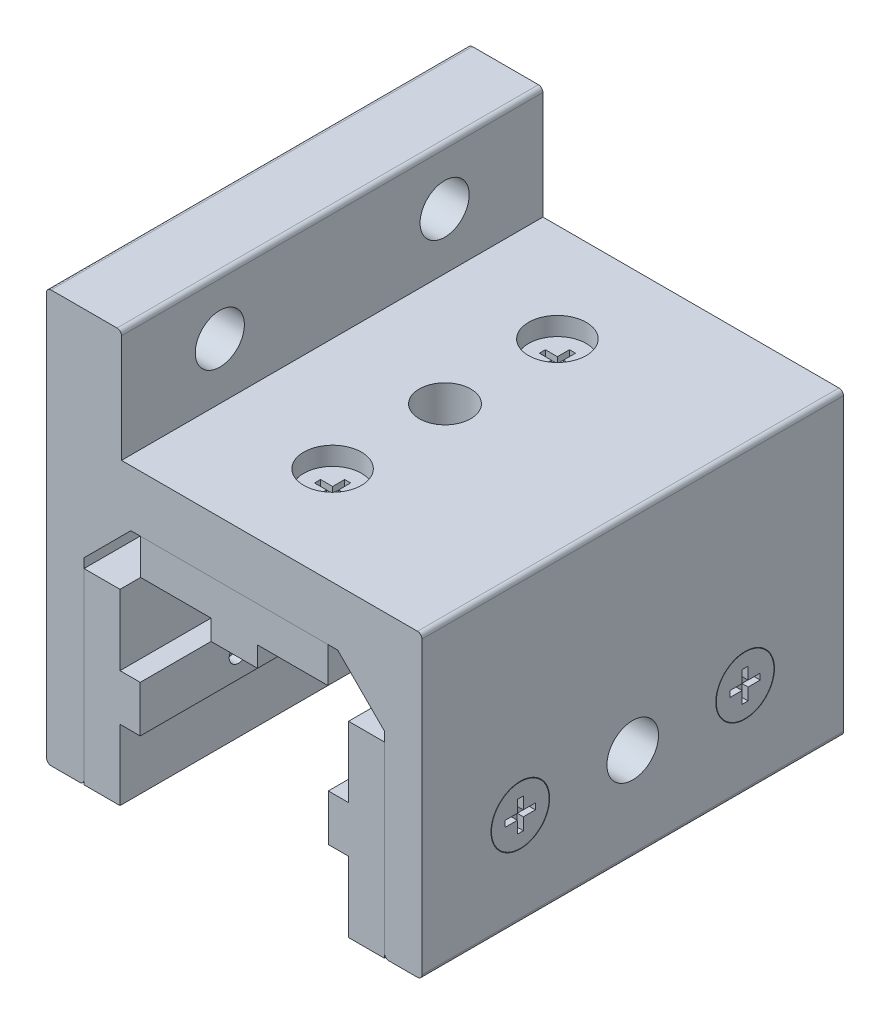
SolidWorks part; units mm, degrees
ref_plane "Front Plane" through (0, 0, 0) normal (0, 0, 1) x (1, 0, 0)
ref_plane "Top Plane" through (0, 0, 0) normal (0, 1, 0) x (1, 0, 0)
ref_plane "Right Plane" through (0, 0, 0) normal (1, 0, 0) x (0, 0, -1)
sketch "Sketch1" plane through (0, 0, 0) normal (0, 0, 1) x (1, 0, 0)
  line L0 (0, -34.925) -> (0, 34.925) construction
  line L1 (-31.8135, 0) -> (31.8135, 0) construction
  line L2 (-31.8135, 34.925) -> (-31.8135, -34.925) construction
  line L3 (-31.8135, -34.925) -> (-25.4635, -34.925) construction
  line L4 (-25.4635, -34.925) -> (-25.4635, -1.5875) construction
  line L5 (-25.4635, -1.5875) -> (-17.526, 6.35) construction
  line L6 (-17.526, 6.35) -> (17.526, 6.35) construction
  line L7 (17.526, 6.35) -> (25.4635, -1.5875) construction
  line L8 (25.4635, -1.5875) -> (25.4635, -34.925) construction
  line L9 (25.4635, -34.925) -> (31.8135, -34.925) construction
  line L10 (31.8135, -34.925) -> (31.8135, 15.875) construction
  line L11 (31.8135, 15.875) -> (-19.1135, 15.875) construction
  line L12 (-19.1135, 15.875) -> (-19.1135, 34.925) construction
  line L13 (-19.1135, 34.925) -> (-31.8135, 34.925) construction
  line L14 (-25.4635, -3.175) -> (-19.3675, -3.175) construction
  line L15 (-19.3675, -3.175) -> (-19.3675, -15.113) construction
  line L16 (-19.3675, -15.113) -> (-15.9385, -15.113) construction
  line L17 (-15.9385, -15.113) -> (-15.9385, -22.987) construction
  line L18 (-15.9385, -22.987) -> (-19.3675, -22.987) construction
  line L19 (-19.3675, -22.987) -> (-19.3675, -34.925) construction
  line L20 (-19.3675, -34.925) -> (-25.4635, -34.925) construction
  line L21 (-19.3675, -15.113) -> (-19.3675, -22.987) construction
  line L22 (-15.9385, -19.05) -> (-25.4635, -19.05) construction
  line L23 (-25.4635, -19.05) -> (25.4635, -19.05) construction
  point P4 (0, 0)
  point P7 (0, 0)
  point P30 (0, 6.35)
  point P31 (0, 12.7)
  dimension "Length (B)" = 69.85
  dimension "Length (A)" = 63.627
  dimension "Mounting Hole Depth" = 12.7
  dimension "D1" = 6.35
  dimension "Chamfer" = 7.9375
  dimension "D2" = 45
  dimension "Inner Height" = 41.275
  dimension "Pad Width" = 31.75
  dimension "Pad Height" = 9.525
  dimension "Pad Thickness" = 6.096
  dimension "Pad Rail" = 7.874
  dimension "Countersink Depth" = 3.175
  dimension "Length (C)" = 50.8
sketch "Sketch2" plane through (0, 0, 0) normal (1, 0, 0) x (0, 0, -1)
  line L0 (-35.7124, 0) -> (35.7124, 0) construction
  line L1 (-35.7124, 15.875) -> (35.7124, 15.875) construction
  line L2 (-35.7124, 34.925) -> (35.7124, 34.925) construction
  line L3 (-35.7124, 34.925) -> (-35.7124, -34.925) construction
  line L4 (-35.7124, -34.925) -> (35.7124, -34.925) construction
  line L5 (35.7124, 34.925) -> (35.7124, -34.925) construction
  line L7 (0, 34.925) -> (0, 15.875) construction
  line L8 (-19.05, 25.4) -> (19.05, 25.4) construction
  line L9 (-35.7124, -19.05) -> (35.7124, -19.05) construction
  line L10 (-19.5605, -21.6027) -> (-18.5395, -21.6027) construction
  line L11 (-19.5605, -21.6027) -> (-19.5605, -16.4973) construction
  line L12 (-19.5605, -16.4973) -> (-18.5395, -16.4973) construction
  line L13 (-18.5395, -21.6027) -> (-18.5395, -16.4973) construction
  line L14 (-19.05, -16.4973) -> (-19.05, -21.6027) construction
  line L15 (-19.5605, -19.05) -> (-18.5395, -19.05) construction
  line L16 (-21.6027, -18.5395) -> (-16.4973, -18.5395) construction
  line L17 (-21.6027, -18.5395) -> (-21.6027, -19.5605) construction
  line L18 (-21.6027, -19.5605) -> (-16.4973, -19.5605) construction
  line L19 (-16.4973, -18.5395) -> (-16.4973, -19.5605) construction
  line L20 (-19.05, -19.5605) -> (-19.05, -18.5395) construction
  line L21 (-21.6027, -19.05) -> (-16.4973, -19.05) construction
  circle A0 centre (-19.05, 25.4) radius 4.1656 construction
  circle A1 centre (19.05, 25.4) radius 4.1656 construction
  circle A2 centre (0, -19.05) radius 4.3688 construction
  circle A3 centre (-19.05, -19.05) radius 2.5527 construction
  circle A4 centre (19.05, -19.05) radius 2.5527 construction
  circle A5 centre (19.05, -19.05) radius 1.5875
  circle A6 centre (-19.05, -19.05) radius 1.5875
  point P12 (0, 15.875)
  point P16 (0, 25.4)
  point P19 (0, 25.4)
  point P22 (0, -19.05)
  dimension "Mounting Hole Diameter" = 8.3312
  dimension "Hole Diameter 2" = 8.7376
  dimension "D1" = 5.1054
  dimension "Pilot Hole" = 3.175
  dimension "Length" = 71.4248
  dimension "Mounting Hole Spacing" = 38.1
  dimension "D2" = 1.0211
sketch "Sketch3" plane through (0, 0, 0) normal (0, 1, 0) x (1, 0, 0)
  line L0 (0, -35.7124) -> (0, 35.7124) construction
  line L5 (0, -35.7124) -> (0, 35.7124) construction
  line L6 (-31.8135, 0) -> (31.8135, 0) construction
  circle A0 centre (0, 19.05) radius 2.5527 construction
  circle A1 centre (0, -19.05) radius 2.5527 construction
  circle A2 centre (0, 0) radius 4.3688 construction
  circle A3 centre (0, 19.05) radius 4.8895 construction
  circle A4 centre (0, -19.05) radius 4.8895 construction
  dimension "D1" = 8.7376
  dimension "D2" = 5.1054
  dimension "Countersink Diameter" = 9.779
ref_plane "Plane1" through (0, 0, 19.05) normal (0, 0, 1) x (1, 0, 0)
sketch "Sketch11" plane through (0, 0, 19.05) normal (0, 0, 1) x (1, 0, 0)
  line L0 (-25.4635, -19.05) -> (-31.8135, -19.05) construction
  line L1 (-31.8135, 34.925) -> (-31.8135, -34.925) construction
  line L2 (-31.8135, -14.1605) -> (-31.8135, -23.9395) construction
  line L3 (-31.8135, -14.1605) -> (-29.7355, -16.637) construction
  line L4 (-29.7355, -16.637) -> (-29.7355, -21.463) construction
  line L5 (-29.7355, -21.463) -> (-31.8135, -23.9395) construction
  line L6 (-29.7355, -16.637) -> (-17.653, -16.637) construction
  line L7 (-17.653, -16.637) -> (-17.653, -15.113) construction
  line L8 (-19.3675, -15.113) -> (-15.9385, -15.113) construction
  point P7 (-30.7745, -15.3987)
  dimension "D1" = 9.779
  dimension "D2" = 100
  dimension "D3" = 4.826
sketch "Sketch4" plane through (0, 0, 0) normal (0, 0, 1) x (1, 0, 0)
  line L0 (-31.8135, -34.925) -> (-25.4635, -34.925) construction
  line L1 (-31.8135, 34.925) -> (-31.8135, -34.925) construction
  line L2 (-19.1135, 34.925) -> (-31.8135, 34.925) construction
  line L3 (-19.1135, 15.875) -> (-19.1135, 34.925) construction
  line L4 (31.8135, 15.875) -> (-19.1135, 15.875) construction
  line L5 (31.8135, -34.925) -> (31.8135, 15.875) construction
  line L6 (25.4635, -34.925) -> (31.8135, -34.925) construction
  line L7 (25.4635, -1.5875) -> (25.4635, -34.925) construction
  line L8 (17.526, 6.35) -> (25.4635, -1.5875) construction
  line L9 (-17.526, 6.35) -> (17.526, 6.35) construction
  line L10 (-25.4635, -1.5875) -> (-17.526, 6.35) construction
  line L11 (-25.4635, -34.925) -> (-25.4635, -1.5875) construction
  line L12 (-31.8135, -34.925) -> (-25.4635, -34.925)
  line L13 (-31.8135, 34.925) -> (-31.8135, -34.925)
  line L14 (-19.1135, 34.925) -> (-31.8135, 34.925)
  line L15 (-19.1135, 15.875) -> (-19.1135, 34.925)
  line L16 (31.8135, 15.875) -> (-19.1135, 15.875)
  line L17 (31.8135, -34.925) -> (31.8135, 15.875)
  line L18 (25.4635, -34.925) -> (31.8135, -34.925)
  line L19 (25.4635, -1.5875) -> (25.4635, -34.925)
  line L20 (17.526, 6.35) -> (25.4635, -1.5875)
  line L21 (-17.526, 6.35) -> (17.526, 6.35)
  line L22 (-25.4635, -1.5875) -> (-17.526, 6.35)
  line L23 (-25.4635, -34.925) -> (-25.4635, -1.5875)
extrude "Boss-Extrude1" add sketch "Sketch4" against normal up to vertex (35.7124 mm away) and the other way up to vertex (35.7124 mm away) up to point (0, 0, -35.7124) other way up to point (0, -34.925, 35.7124)
sketch "Sketch5" plane through (0, 0, 0) normal (0, 0, 1) x (1, 0, 0)
  line L0 (-25.4635, -3.175) -> (-25.4635, -34.925)
  line L1 (-25.4635, -34.925) -> (-19.3675, -34.925)
  line L2 (-19.3675, -34.925) -> (-19.3675, -22.987)
  line L3 (-19.3675, -22.987) -> (-15.9385, -22.987)
  line L4 (-15.9385, -22.987) -> (-15.9385, -15.113)
  line L5 (-15.9385, -15.113) -> (-19.3675, -15.113)
  line L6 (-19.3675, -15.113) -> (-19.3675, -3.175)
  line L7 (-19.3675, -3.175) -> (-25.4635, -3.175)
extrude "Boss-Extrude2" add sketch "Sketch5" along normal up to vertex (35.7124 mm away) and the other way up to vertex (35.7124 mm away) separate body up to point (0, -34.925, 35.7124) other way up to point (0, -34.925, -35.7124)
sketch "Sketch6" plane through (0, 0, 0) normal (1, 0, 0) x (0, 0, -1)
  circle A0 centre (-19.05, -19.05) radius 2.5527 construction
  circle A1 centre (0, -19.05) radius 4.3688 construction
  circle A2 centre (19.05, -19.05) radius 2.5527 construction
  circle A3 centre (19.05, 25.4) radius 4.1656 construction
  circle A4 centre (-19.05, 25.4) radius 4.1656 construction
  circle A5 centre (-19.05, -19.05) radius 2.5527
  circle A6 centre (0, -19.05) radius 4.3688
  circle A7 centre (19.05, -19.05) radius 2.5527
  circle A8 centre (19.05, 25.4) radius 4.1656
  circle A9 centre (-19.05, 25.4) radius 4.1656
extrude "Cut-Extrude1" cut sketch "Sketch6" against normal through all both and the other way through all
sketch "Sketch7" plane through (0, 0, 0) normal (1, 0, 0) x (0, 0, -1)
  line L1 (-4.3688, -23.4188) -> (4.3688, -23.4188)
  line L2 (-4.3688, -23.4188) -> (-4.3688, -14.6812)
  line L3 (-4.3688, -14.6812) -> (4.3688, -14.6812)
  line L4 (4.3688, -23.4188) -> (4.3688, -14.6812)
  line L5 (0, -14.6812) -> (0, -23.4188) construction
  line L6 (-4.3688, -19.05) -> (4.3688, -19.05) construction
  circle A0 centre (-19.05, -19.05) radius 1.5875 construction
  circle A1 centre (-19.05, -19.05) radius 1.5875
  circle A2 centre (19.05, -19.05) radius 1.5875 construction
  circle A3 centre (19.05, -19.05) radius 1.5875
  circle A4 centre (0, -19.05) radius 4.3688 construction
  point P6 (0, -19.05)
extrude "Cut-Extrude2" cut sketch "Sketch7" against normal through all
sketch "Sketch8" plane through (0, 15.875, 0) normal (0, 1, 0) x (1, 0, 0)
  circle A0 centre (0, 19.05) radius 2.5527 construction
  circle A1 centre (0, -19.05) radius 2.5527 construction
  circle A2 centre (0, 19.05) radius 2.5527
  circle A3 centre (0, -19.05) radius 2.5527
extrude "Cut-Extrude3" cut sketch "Sketch8" against normal up to vertex (9.525 mm away) up to point (0, 6.35, 0)
sketch "Sketch9" plane through (0, 15.875, 0) normal (0, 1, 0) x (1, 0, 0)
  circle A0 centre (0, 19.05) radius 4.8895 construction
  circle A1 centre (0, 19.05) radius 4.8895
  circle A2 centre (0, -19.05) radius 4.8895 construction
  circle A3 centre (0, -19.05) radius 4.8895
extrude "Cut-Extrude4" cut sketch "Sketch9" against normal up to vertex (3.175 mm away) up to point (0, 12.7, 0)
chamfer "Chamfer1" distance 2.032 angle 50 6 edges at (-31.8135, -19.05, -21.6027) (-31.8135, -19.05, 16.4973) (31.8135, -19.05, -21.6027) (31.8135, -19.05, 16.4973) (-2.5527, 12.7, 19.05) (-2.5527, 12.7, -19.05)
sketch "Sketch12" plane through (0, 0, 19.05) normal (0, 0, 1) x (1, 0, 0)
  line L0 (-31.8135, -14.1605) -> (-31.8135, -19.05)
  line L1 (-31.8135, -19.05) -> (-17.653, -19.05)
  line L2 (-17.653, -19.05) -> (-17.653, -16.637)
  line L3 (-17.653, -16.637) -> (-29.7355, -16.637)
  line L4 (-29.7355, -16.637) -> (-31.8135, -14.1605)
revolve "Revolve1" add sketch "Sketch12" angle 360 about L1
sketch "Sketch13" plane through (-31.8135, 0, 0) normal (-1, 0, 0) x (0, 0, 1)
  line L0 (19.5605, -21.6027) -> (18.5395, -21.6027) construction
  line L1 (19.5605, -21.6027) -> (19.5605, -16.4973) construction
  line L2 (19.5605, -16.4973) -> (18.5395, -16.4973) construction
  line L3 (18.5395, -21.6027) -> (18.5395, -16.4973) construction
  line L4 (19.5605, -21.6027) -> (18.5395, -21.6027)
  line L5 (19.5605, -21.6027) -> (19.5605, -19.5605)
  line L6 (19.5605, -16.4973) -> (18.5395, -16.4973)
  line L7 (18.5395, -21.6027) -> (18.5395, -19.5605)
  line L8 (21.6027, -18.5395) -> (21.6027, -19.5605) construction
  line L9 (21.6027, -19.5605) -> (16.4973, -19.5605) construction
  line L10 (16.4973, -18.5395) -> (16.4973, -19.5605) construction
  line L11 (21.6027, -18.5395) -> (16.4973, -18.5395) construction
  line L12 (21.6027, -18.5395) -> (21.6027, -19.5605)
  line L13 (21.6027, -19.5605) -> (19.5605, -19.5605)
  line L14 (16.4973, -18.5395) -> (16.4973, -19.5605)
  line L15 (21.6027, -18.5395) -> (19.5605, -18.5395)
  line L16 (18.5395, -18.5395) -> (16.4973, -18.5395)
  line L17 (18.5395, -18.5395) -> (18.5395, -16.4973)
  line L18 (18.5395, -19.5605) -> (16.4973, -19.5605)
  line L19 (19.5605, -18.5395) -> (19.5605, -16.4973)
extrude "Cut-Extrude5" cut sketch "Sketch13" against normal up to vertex (1.039 mm away) up to point (-30.7745, -15.3987, 19.05)
pattern_linear "LPattern1" count 2 spacing 38.1 along (0, 0, -1) of bodies 111
pattern_circular "CirPattern1" count 3 over 180 about axis through (0, -19.05, 0) along (0, 0, 1) of bodies 107 111 112
fillet "Fillet1" radius 0.762 7 edges at (-19.1135, 34.925, 0) (-31.8135, 34.925, 0) (31.8135, 15.875, 0) (31.8135, -34.925, 0) (25.4635, -34.925, 0) (-25.4635, -34.925, 0) (-31.8135, -34.925, 0)
sketch "Sketch14" plane through (0, 15.875, 0) normal (0, 1, 0) x (1, 0, 0)
  circle A0 centre (0, 0) radius 4.3688
  circle A1 centre (0, 0) radius 4.3688 construction
extrude "Cut-Extrude6" cut sketch "Sketch14" against normal through all
equation "\"D1@Sketch1\" = \"Mounting Hole Depth@Sketch1\" / 2"
equation "\"D1@Sketch3\"=\"Hole Diameter 2@Sketch2\""
equation "\"D2@Sketch3\"=\"D1@Sketch2\""
equation "\"D2@Sketch2\"=\"D1@Sketch2\"*.2"
equation "\"D1@Sketch11\"=\"Countersink Diameter@Sketch3\""
equation "\"D3@LPattern1\"=\"Mounting Hole Spacing@Sketch2\""
equation "\"Chamfer@Sketch1\"=\"Mounting Hole Depth@Sketch1\"*.625"
